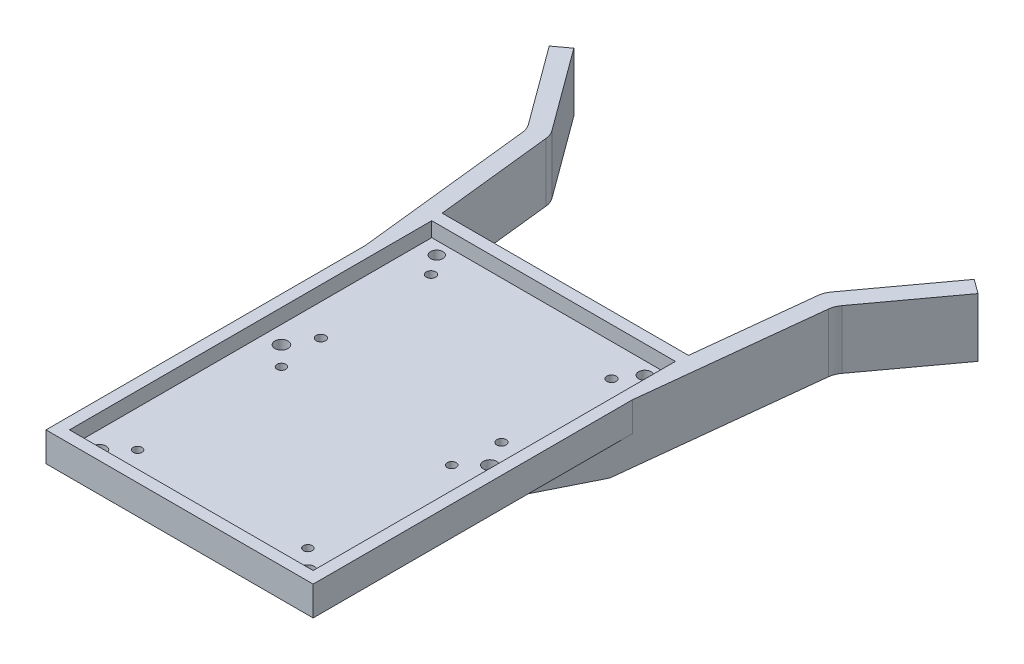
SolidWorks part; units mm, degrees
material "ABS"
ref_plane "前视基准面" through (0, 0, 0) normal (0, 0, 1) x (1, 0, 0)
ref_plane "上视基准面" through (0, 0, 0) normal (0, 1, 0) x (1, 0, 0)
ref_plane "右视基准面" through (0, 0, 0) normal (1, 0, 0) x (0, 0, -1)
sketch "Sketch1" plane through (0, 0, 0) normal (0, 1, 0) x (1, 0, 0)
  line L1 (-45.5, 39.2) -> (45.5, 39.2)
  line L2 (-45.5, 39.2) -> (-45.5, -39.2)
  line L3 (-45.5, -39.2) -> (45.5, -39.2)
  line L4 (45.5, 39.2) -> (45.5, -39.2)
  line L5 (0, -39.2) -> (0, 39.2) construction
  line L6 (-45.5, 0) -> (45.5, 0) construction
  circle A4 centre (-29, -24.5) radius 1.5
  circle A5 centre (29, -24.5) radius 1.5
  circle A6 centre (-29, 24.5) radius 1.5
  circle A7 centre (29, 24.5) radius 1.5
  point P0 (0, 0)
  dimension "D1" = 78.4
  dimension "D2" = 91
extrude "Boss-Extrude1" add sketch "Sketch1" along normal blind 10
sketch "Sketch2" plane through (0, 10, 0) normal (0, 1, 0) x (1, 0, 0)
  line L0 (45.5, 39.2) -> (-45.5, 39.2) construction
  line L1 (-41.5, 39.2) -> (41.5, 39.2)
  line L8 (41.5, -35.2) -> (41.5, 35.2)
  line L9 (41.5, 35.2) -> (-41.5, 35.2)
  line L10 (-41.5, 35.2) -> (-41.5, -35.2)
  line L11 (-41.5, -35.2) -> (41.5, -35.2)
  line L12 (41.5, -35.2) -> (41.5, 39.2)
  line L14 (-41.5, 39.2) -> (-41.5, -35.2)
  line L15 (-41.5, -35.2) -> (41.5, -35.2)
  dimension "D1" = 4
extrude "Cut-Extrude1" cut sketch "Sketch2" against normal blind 5
sketch "Sketch3" plane through (0, 0, 0) normal (0, -1, 0) x (1, 0, 0)
  line L1 (35.5, -31) -> (-35.5, -31) construction
  line L2 (35.5, -31) -> (35.5, 31) construction
  line L3 (35.5, 31) -> (-35.5, 31) construction
  line L4 (-35.5, -31) -> (-35.5, 31) construction
  line L5 (0, 31) -> (0, -31) construction
  line L6 (35.5, 0) -> (-35.5, 0) construction
  circle A0 centre (35.5, 31) radius 2.25
  circle A1 centre (-35.5, 31) radius 2.25
  circle A2 centre (-35.5, -31) radius 2.25
  circle A3 centre (35.5, -31) radius 2.25
  point P0 (0, 0)
  dimension "D3" = 4.5
  dimension "D1" = 71
  dimension "D2" = 62
extrude "Cut-Extrude2" cut sketch "Sketch3" against normal up to next
sketch "Sketch4" plane through (0, 0, -39.2) normal (0, 0, -1) x (-1, 0, 0)
  line L4 (41.5, 5) -> (-41.5, 5)
  line L8 (45.5, 10) -> (41.5, 10)
  line L9 (41.5, 10) -> (41.5, 5)
  line L12 (41.5, 5) -> (-41.5, 5)
  line L13 (-41.5, 5) -> (-41.5, 10)
  line L14 (-41.5, 5) -> (-41.5, 10)
  line L15 (45.5, 0) -> (45.5, 10)
  line L16 (45.5, 10) -> (41.5, 10)
  line L17 (41.5, 10) -> (41.5, 5)
  line L23 (45.5, 0) -> (45.5, 10)
  line L24 (-41.5, 10) -> (-45.5, 10)
  line L25 (-41.5, 10) -> (-45.5, 10)
  line L26 (-45.5, 10) -> (-45.5, 0)
  line L27 (-45.5, 10) -> (-45.5, 0)
  line L28 (-45.5, 0) -> (45.5, 0)
  line L29 (-45.5, 0) -> (45.5, 0)
  dimension "D1" = 0
extrude "Boss-Extrude2" add sketch "Sketch4" along normal blind 49
sketch "Sketch5" plane through (0, 0, -88.2) normal (0, 0, -1) x (-1, 0, 0)
  line L0 (-45.5, 0) -> (45.5, 0) construction
  line L1 (-45.5, 10) -> (45.5, 10)
  line L2 (-45.5, 10) -> (-45.5, 0)
  line L3 (-45.5, 0) -> (45.5, 0)
  line L4 (45.5, 10) -> (45.5, 0)
  line L5 (45.5, 10) -> (41.5, 10) construction
  line L7 (-45.5, 10) -> (-45.5, 0) construction
extrude "Boss-Extrude3" add sketch "Sketch5" along normal blind 4
sketch "Sketch8" plane through (0, 5, 0) normal (0, 1, 0) x (1, 0, 0)
  line L0 (-35.5, 31) -> (-35.5, -31) construction
  line L2 (35.5, 31) -> (-35.5, 31) construction
  line L3 (34.2, 80.9) -> (-34.2, 80.9) construction
  line L4 (34.2, 80.9) -> (34.2, 36) construction
  line L5 (34.2, 36) -> (-34.2, 36) construction
  line L6 (-34.2, 80.9) -> (-34.2, 36) construction
  line L7 (0, 36) -> (0, 80.9) construction
  line L8 (34.2, 58.45) -> (-34.2, 58.45) construction
  circle A0 centre (-35.5, 83.9) radius 2.1
  circle A1 centre (35.3688, 83.9) radius 2.1
  point P7 (0, 58.45)
  dimension "D1" = 4.2
  dimension "D2" = 68.4
  dimension "D3" = 44.9
  dimension "D4" = 5
  dimension "D5" = 3
extrude "Cut-Extrude4" cut sketch "Sketch8" against normal up to next
sketch "Sketch9" plane through (0, 0, 0) normal (0, -1, 0) x (1, 0, 0)
  circle A4 centre (-30.75, -77.2) radius 1.6
  circle A5 centre (-30.75, -39.7) radius 1.6
  circle A6 centre (30.75, -39.7) radius 1.6
  circle A7 centre (30.75, -77.2) radius 1.6
extrude "Cut-Extrude5" cut sketch "Sketch9" against normal up to next
sketch "Sketch10" plane through (0, 0, 0) normal (0, -1, 0) x (1, 0, 0)
  line L0 (45.5, -69.5003) -> (52.1195, -129.7066)
  line L1 (53.4049, -133.0079) -> (73.0277, -159.7463)
  line L2 (73.0277, -159.7463) -> (68.1906, -163.2962)
  line L3 (68.1906, -163.2962) -> (47.6166, -135.2617)
  line L4 (46.3312, -131.9604) -> (41.9596, -92.2)
  line L7 (45.5, 39.2) -> (45.5, -92.2) construction
  line L8 (-45.5, -92.2) -> (45.5, -92.2) construction
  line L9 (0, 0) -> (0, -114.1838) construction
  line L10 (-46.3312, -131.9604) -> (-41.9596, -92.2)
  line L11 (-68.1906, -163.2962) -> (-47.6166, -135.2617)
  line L12 (-73.0277, -159.7463) -> (-68.1906, -163.2962)
  line L13 (-53.4049, -133.0079) -> (-73.0277, -159.7463)
  line L14 (-45.5, -69.5003) -> (-52.1195, -129.7066)
  line L15 (41.9596, -92.2) -> (45.5, -92.2)
  line L16 (45.5, -92.2) -> (45.5, -69.5003)
  line L17 (-41.9596, -92.2) -> (-45.5, -92.2)
  line L18 (-45.5, -92.2) -> (-45.5, -69.5003)
  arc A0 (47.6166, -135.2617) -> (46.3312, -131.9604) centre (53.1342, -131.2124) cw
  arc A1 (52.1195, -129.7066) -> (53.4049, -133.0079) centre (58.9226, -128.9586) ccw
  arc A2 (-52.1195, -129.7066) -> (-53.4049, -133.0079) centre (-58.9226, -128.9586) cw
  arc A3 (-47.6166, -135.2617) -> (-46.3312, -131.9604) centre (-53.1342, -131.2124) ccw
  point P13 (52.3199, -131.5295)
  point P29 (-52.3199, -131.5295)
  dimension "D2" = 35
  dimension "D3" = 6
  dimension "D4" = 6
  dimension "D6" = 40
  dimension "D1" = 150
extrude "Boss-Extrude4" add sketch "Sketch10" against normal up to surface (10 mm away) and the other way blind 10 up to face at (0, 10, -26.5)
chamfer "Chamfer1" distance 5 angle 67 1 edges at (45.5, 0, -80.8502) first distance on face at (30.75, 0, -78.8)
fillet "Fillet1" radius 10 1 edges at (43.3522, -6.7193, -92.2)
chamfer "Chamfer2" distance 5 angle 67 1 edges at (-45.5, 0, -80.8502) first distance on face at (30.75, 0, -78.8)
fillet "Fillet2" radius 10 1 edges at (-43.3522, -6.7193, -92.2)
equation "\"D4@Sketch10\"=\"D3@Sketch10\""
